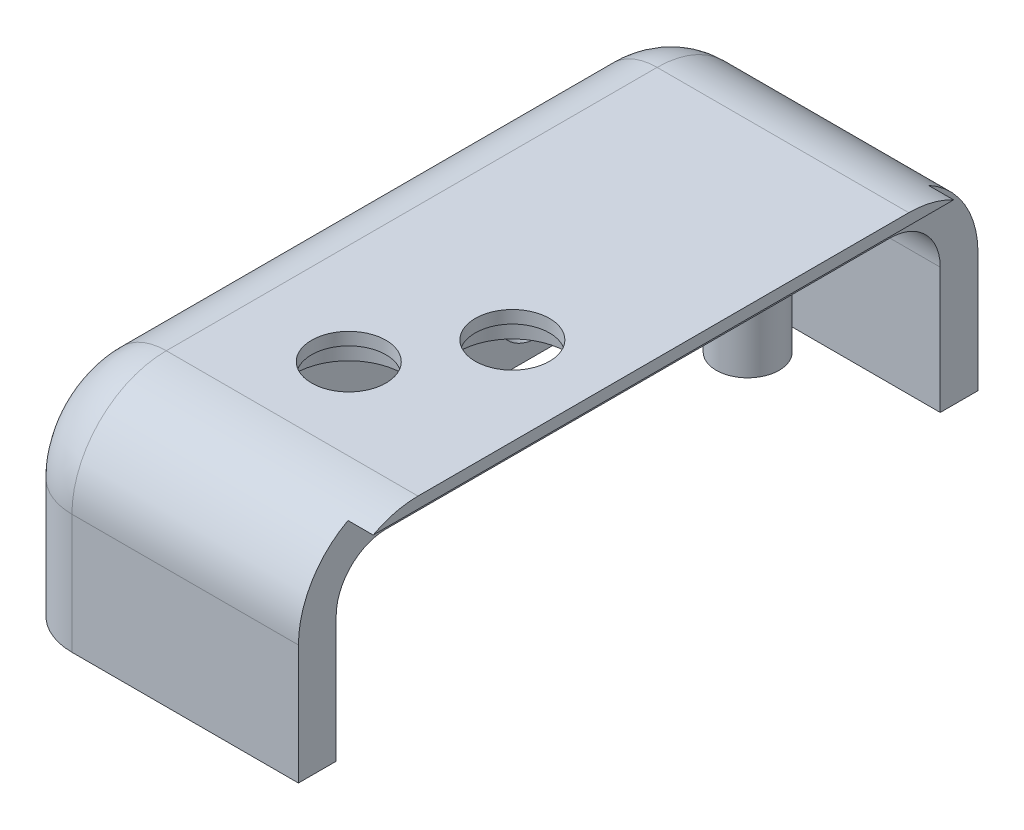
SolidWorks part; units mm, degrees
material "ABS"
ref_plane "Front Plane" through (0, 0, 0) normal (0, 0, 1) x (1, 0, 0)
ref_plane "Top Plane" through (0, 0, 0) normal (0, 1, 0) x (1, 0, 0)
ref_plane "Right Plane" through (0, 0, 0) normal (1, 0, 0) x (0, 0, -1)
sketch "Sketch1" plane through (0, 0, 0) normal (0, 1, 0) x (1, 0, 0)
  line L1 (0, 0) -> (58.42, 0)
  line L2 (0, 0) -> (0, 137.16)
  line L3 (0, 137.16) -> (58.42, 137.16)
  line L4 (58.42, 0) -> (58.42, 137.16)
  dimension "D1" = 137.16
  dimension "D2" = 58.42
extrude "Boss-Extrude1" add sketch "Sketch1" along normal blind 7.62
sketch "Sketch2" plane through (0, 0, 0) normal (0, -1, 0) x (1, 0, 0)
  line L0 (0, -137.16) -> (0, 0) construction
  line L1 (58.42, -137.16) -> (0, -137.16) construction
  circle A0 centre (28.448, -120.65) radius 6.35
  circle A1 centre (28.448, -120.65) radius 4.826
  circle A2 centre (28.448, -15.24) radius 6.35
  circle A3 centre (28.448, -15.24) radius 4.826
  dimension "D1" = 12.7
  dimension "D2" = 9.652
  dimension "D3" = 12.7
  dimension "D4" = 9.652
  dimension "D5" = 28.448
  dimension "D6" = 105.41
  dimension "D7" = 16.51
extrude "Boss-Extrude2" add sketch "Sketch2" along normal blind 35.56
sketch "Sketch3" plane through (0, 0, 0) normal (0, -1, 0) x (1, 0, 0)
  line L0 (58.42, -137.16) -> (0, -137.16)
  line L1 (0, -137.16) -> (0, 0)
  line L2 (0, 0) -> (58.42, 0)
  line L3 (58.42, 0) -> (58.42, -7.62)
  line L4 (58.42, 0) -> (58.42, -137.16) construction
  line L5 (58.42, -7.62) -> (7.62, -7.62)
  line L6 (7.62, -7.62) -> (7.62, -129.54)
  line L7 (7.62, -129.54) -> (58.42, -129.54)
  line L8 (58.42, -129.54) -> (58.42, -137.16)
  dimension "D1" = 7.62
  dimension "D2" = 7.62
  dimension "D3" = 7.62
extrude "Boss-Extrude3" add sketch "Sketch3" along normal blind 35.56
fillet "Fillet1" radius 19.05 2 edges at (29.21, 7.62, 0) (29.21, 7.62, -137.16)
fillet "Fillet2" radius 12.7 5 edges at (0, 2.0404, -5.5796) (0, 2.0404, -131.5804) (0, -23.495, 0) (0, 7.62, -68.58) (0, -23.495, -137.16)
sketch "Sketch4" plane through (58.42, 0, 0) normal (1, 0, 0) x (0, 0, -1)
  line L1 (10.0018, 5.334) -> (127.1582, 5.334)
  line L3 (19.05, 7.62) -> (118.11, 7.62)
  line L6 (19.05, 7.62) -> (118.11, 7.62) construction
  arc A0 (137.16, -11.43) -> (118.11, 7.62) centre (118.11, -11.43) ccw construction
  arc A1 (19.05, 7.62) -> (0, -11.43) centre (19.05, -11.43) ccw construction
  arc A2 (118.11, 7.62) -> (127.1582, 5.334) centre (118.11, -11.43) cw
  arc A3 (19.05, 7.62) -> (10.0018, 5.334) centre (19.05, -11.43) ccw
  dimension "D1" = 2.286
extrude "Boss-Extrude4" add sketch "Sketch4" along normal blind 5.08
sketch "Sketch7" plane through (0, 7.62, 0) normal (0, 1, 0) x (1, 0, 0)
  line L1 (58.42, 0) -> (12.7, 0) construction
  line L4 (0, 19.05) -> (0, 118.11) construction
  circle A2 centre (45.72, 55.88) radius 7.5
  circle A3 centre (33.02, 35.56) radius 7.5
  dimension "D1" = 15
  dimension "D2" = 15
  dimension "D3" = 12.7
  dimension "D4" = 33.02
  dimension "D9" = 20.32
  dimension "D10" = 35.56
extrude "Cut-Extrude1" cut sketch "Sketch7" against normal through all
sketch "Sketch8" plane through (0, 0, 0) normal (0, -1, 0) x (1, 0, 0)
  circle A6 centre (45.72, -55.88) radius 7.5
  circle A7 centre (45.72, -55.88) radius 11
  circle A8 centre (33.02, -35.56) radius 7.5
  circle A9 centre (33.02, -35.56) radius 11
  circle A10 centre (45.72, -55.88) radius 7.5 construction
  circle A12 centre (33.02, -35.56) radius 7.5 construction
  circle A15 centre (45.72, -55.88) radius 7.5 construction
  circle A16 centre (33.02, -35.56) radius 7.5 construction
  dimension "D3" = 22
  dimension "D4" = 22
extrude "Cut-Extrude2" cut sketch "Sketch8" against normal blind 5.08
fillet "Fillet3" radius 10.16 5 edges at (33.02, 0, -129.54) (33.02, 0, -7.62) (7.62, 0, -68.58) (7.62, -17.78, -7.62) (7.62, -17.78, -129.54)
sketch "Sketch9" plane through (0, 0, 0) normal (-1, 0, 0) x (0, 0, 1)
  line L1 (-12.7, -35.56) -> (-124.46, -35.56) construction
  line L2 (-137.16, -35.56) -> (-137.16, -11.43) construction
  circle A0 centre (-99.06, -24.13) radius 8.5
  dimension "D1" = 17
  dimension "D2" = 11.43
  dimension "D3" = 38.1
extrude "Cut-Extrude3" cut sketch "Sketch9" against normal up to next
